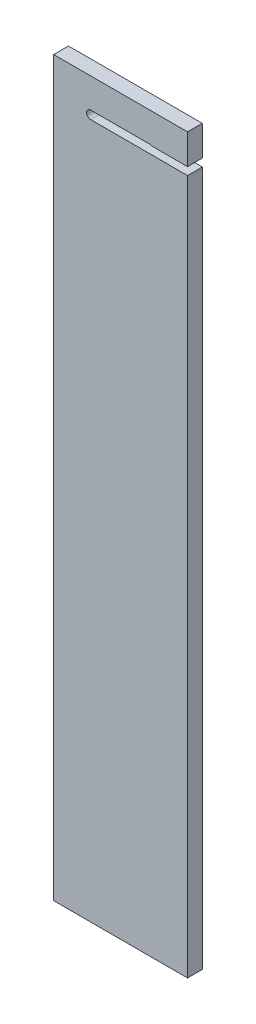
SolidWorks part; units mm, degrees
ref_plane "Front Plane" through (0, 0, 0) normal (0, 0, 1) x (1, 0, 0)
ref_plane "Top Plane" through (0, 0, 0) normal (0, 1, 0) x (1, 0, 0)
ref_plane "Right Plane" through (0, 0, 0) normal (1, 0, 0) x (0, 0, -1)
sketch "Sketch1" plane through (0, 0, 0) normal (0, 0, 1) x (1, 0, 0)
  line L0 (0, 149.225) -> (0, -149.225) construction
  line L1 (-28.75, 149.225) -> (28.75, 149.225)
  line L2 (-28.75, 149.225) -> (-28.75, -149.225)
  line L3 (-28.75, -149.225) -> (28.75, -149.225)
  line L4 (28.75, 149.225) -> (28.75, -149.225)
  line L5 (28.75, 152.527) -> (12.827, 152.527)
  line L10 (0, 149.225) -> (0, 165.481) construction
  line L11 (12.827, 152.527) -> (12.827, 152.781)
  line L12 (-28.75, 149.225) -> (28.75, 149.225)
  line L13 (-28.75, 149.225) -> (-28.75, 165.481)
  line L14 (-28.75, 165.481) -> (28.75, 165.481)
  line L15 (28.75, 149.225) -> (28.75, 165.481)
  line L16 (12.827, 152.781) -> (-12.827, 152.781)
  line L17 (-12.827, 152.781) -> (-12.827, 149.225)
  arc A0 (-12.827, 152.781) -> (-12.827, 149.225) centre (-12.827, 151.003) ccw
  point P6 (0, 0)
  point P21 (0, 152.781)
  dimension "D3" = 12.7
  dimension "D1" = 298.45
  dimension "D2" = 57.5
  dimension "D4" = 0.254
  dimension "D5" = 3.302
  dimension "D6" = 25.654
extrude "Boss-Extrude1" add sketch "Sketch1" along normal blind 6.35 contours L4 L12 L1 L2 L3 | L17 L16 L11 L5 L15 L14 L13 L1 region at (-1.3049, 158.5635, 0) region at (0, 0, 0)
fillet "Fillet1" radius 3.175 1 edges at (12.827, 152.527, 3.175)
equation "\"Height\"= 12in"
equation "\"Depth\"= 7in"
equation "\"WallThickness\"= 0.25in"
equation "\"FloorThickness\"= 0.25in"
equation "\"Width\" = 30in"
equation "\"D1@Boss-Extrude1\"=\"WallThickness\""
